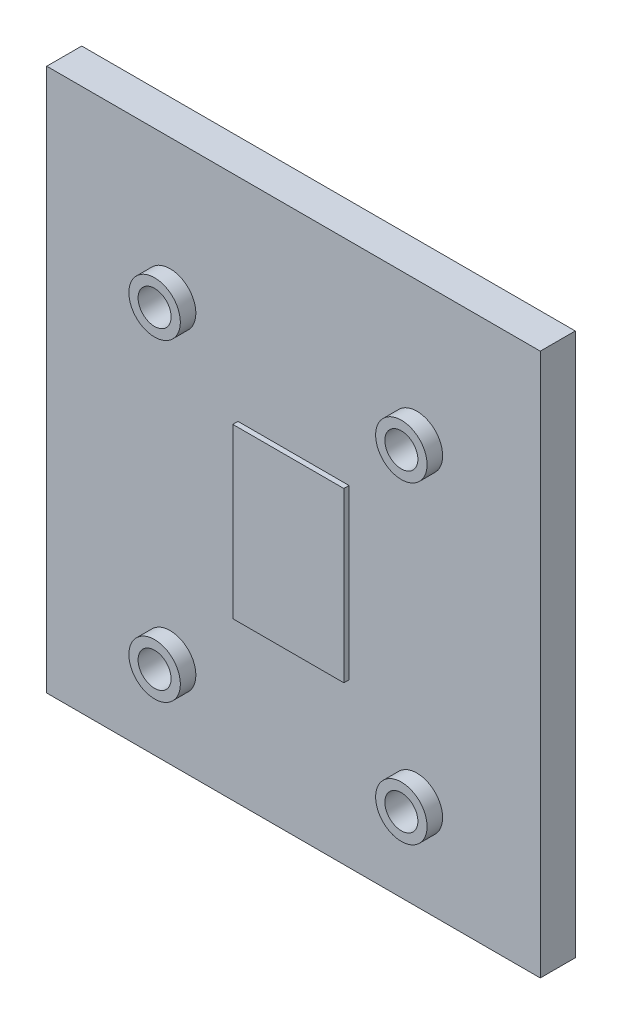
SolidWorks part; units mm, degrees
material "Сталь 08кп ГОСТ 535-88"
ref_plane "Спереди" through (0, 0, 0) normal (0, 0, 1) x (1, 0, 0)
ref_plane "Сверху" through (0, 0, 0) normal (0, 1, 0) x (1, 0, 0)
ref_plane "Справа" through (0, 0, 0) normal (1, 0, 0) x (0, 0, -1)
sketch "Sketch1" plane through (0, 0, 0) normal (0, 0, 1) x (1, 0, 0)
  line L0 (-25.4, -25.4) -> (25.4, -25.4)
  line L1 (25.4, -25.4) -> (25.4, 30.48)
  line L2 (25.4, 30.48) -> (-25.4, 30.48)
  line L3 (-25.4, 30.48) -> (-25.4, -25.4)
extrude "Boss-Extrude1" add sketch "Sketch1" against normal blind 3.6
sketch "Sketch2" plane through (0, 0, 0) normal (0, 0, 1) x (1, 0, 0)
  line L0 (-5.715, 8.6614) -> (5.715, 8.6614)
  line L1 (5.715, 8.6614) -> (5.715, -8.6614)
  line L2 (5.715, -8.6614) -> (-5.715, -8.6614)
  line L3 (-5.715, -8.6614) -> (-5.715, 8.6614)
extrude "Boss-Extrude2" add sketch "Sketch2" along normal blind 0.5332
ref_plane "Plane1" through (0, 16.129, 0) normal (0, -1, 0) x (1, 0, 0)
sketch "Sketch3" plane through (0, 16.129, 0) normal (0, -1, 0) x (1, 0, 0)
  line L0 (-10.052, 1.6) -> (-12.7, 1.6)
  line L1 (-12.7, 1.6) -> (-12.7, 0)
  line L2 (-12.7, 0) -> (-10.052, 0)
  line L3 (-10.052, 0) -> (-10.052, 1.6)
  line L4 (-12.7, 1.6) -> (-12.7, 0) construction
revolve "Revolve1" add sketch "Sketch3" angle 360 about L4 reverse direction yes
ref_plane "Plane2" through (0, -16.129, 0) normal (0, -1, 0) x (1, 0, 0)
sketch "Sketch4" plane through (0, -16.129, 0) normal (0, -1, 0) x (1, 0, 0)
  line L0 (-10.052, 1.6) -> (-12.7, 1.6)
  line L1 (-12.7, 1.6) -> (-12.7, 0)
  line L2 (-12.7, 0) -> (-10.052, 0)
  line L3 (-10.052, 0) -> (-10.052, 1.6)
  line L4 (-12.7, 1.6) -> (-12.7, 0) construction
revolve "Revolve2" add sketch "Sketch4" angle 360 about L4 reverse direction yes
sketch "Sketch5" plane through (0, -16.129, 0) normal (0, -1, 0) x (1, 0, 0)
  line L0 (15.348, 1.6) -> (12.7, 1.6)
  line L1 (12.7, 1.6) -> (12.7, 0)
  line L2 (12.7, 0) -> (15.348, 0)
  line L3 (15.348, 0) -> (15.348, 1.6)
  line L4 (12.7, 1.6) -> (12.7, 0) construction
revolve "Revolve3" add sketch "Sketch5" angle 360 about L4 reverse direction yes
sketch "Sketch6" plane through (0, 16.129, 0) normal (0, -1, 0) x (1, 0, 0)
  line L0 (15.348, 1.6) -> (12.7, 1.6)
  line L1 (12.7, 1.6) -> (12.7, 0)
  line L2 (12.7, 0) -> (15.348, 0)
  line L3 (15.348, 0) -> (15.348, 1.6)
  line L4 (12.7, 1.6) -> (12.7, 0) construction
revolve "Revolve4" add sketch "Sketch6" angle 360 about L4 reverse direction yes
hole_wizard "Ø3.4 (3.4) Diameter Hole1" positions "Sketch8" profile "Sketch7" hole size "Ø3.4" standard "ANSI Metric" end condition through all
sketch "Sketch8" plane through (0, 0, 1.6) normal (0, 0, 1) x (1, 0, 0)
  point P0 (-12.7, -16.129)
  point P1 (12.7, -16.129)
  point P2 (12.7, 16.129)
  point P3 (-12.7, 16.129)
sketch "Sketch7" plane through (-12.7, -16.129, 1.6) normal (1, 0, 0) x (0, -1, 0)
  line L0 (0, 0) -> (0, 5.2)
  line L1 (0, 5.2) -> (1.7, 5.2)
  line L2 (1.7, 5.2) -> (1.7, 0)
  line L5 (1.7, 0) -> (0, 0)
  line L11 (0, -6.35) -> (0, 107.95) construction
  dimension "Thru Hole Dia." = 3.4
  dimension "Thru Hole Depth" = 5.2
